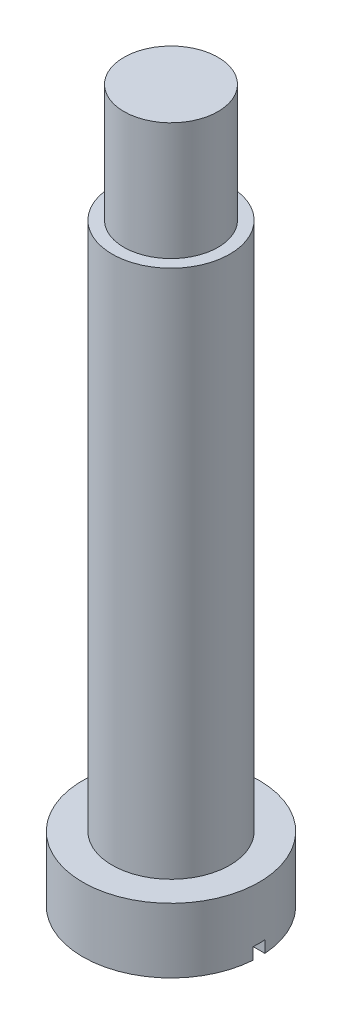
SolidWorks part; units mm, degrees
ref_plane "前视基准面" through (0, 0, 0) normal (0, 0, 1) x (1, 0, 0)
ref_plane "上视基准面" through (0, 0, 0) normal (0, 1, 0) x (1, 0, 0)
ref_plane "右视基准面" through (0, 0, 0) normal (1, 0, 0) x (0, 0, -1)
other "Configuration Table"
sketch "草图1" plane through (0, 0, 0) normal (0, 1, 0) x (1, 0, 0)
  circle A0 centre (0, 0) radius 7.5
  dimension "D1" = 15
extrude "凸台-拉伸1" add sketch "草图1" against normal blind 5.5
sketch "草图2" plane through (0, 0, 0) normal (0, 1, 0) x (1, 0, 0)
  circle A0 centre (0, 0) radius 5
  dimension "D1" = 10
extrude "凸台-拉伸2" add sketch "草图2" along normal blind 45 contours A0
sketch "草图3" plane through (0, 45, 0) normal (0, 1, 0) x (1, 0, 0)
  circle A0 centre (0, 0) radius 4
  dimension "D1" = 8
extrude "凸台-拉伸3" add sketch "草图3" along normal blind 10
sketch "草图4" plane through (0, -5.5, 0) normal (0, -1, 0) x (1, 0, 0)
  line L0 (-7.5, 0) -> (7.5, 0)
  circle A0 centre (0, 0) radius 7.5 construction
extrude "切除-拉伸-薄壁1" cut sketch "草图4" against normal blind 1 and the other way through all thin thin type mid plane wall 1
ref_axis "基准轴1" through (0, 54.9074, 0) along (0, -1, 0)
